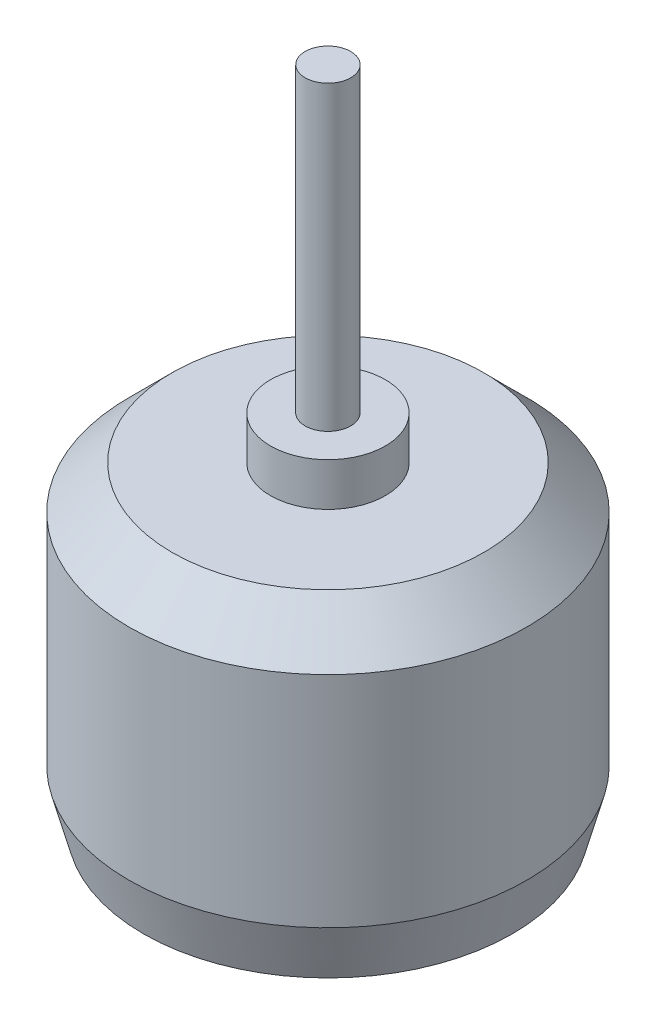
SolidWorks part; units mm, degrees
ref_plane "Front Plane" through (0, 0, 0) normal (0, 0, 1) x (1, 0, 0)
ref_plane "Top Plane" through (0, 0, 0) normal (0, 1, 0) x (1, 0, 0)
ref_plane "Right Plane" through (0, 0, 0) normal (1, 0, 0) x (0, 0, -1)
sketch "Sketch1" plane through (0, 0, 0) normal (0, 1, 0) x (1, 0, 0)
  circle A0 centre (0, 0) radius 13.85
  dimension "D1" = 27.7
extrude "Boss-Extrude1" add sketch "Sketch1" along normal blind 22
sketch "Sketch2" plane through (0, 22, 0) normal (0, 1, 0) x (1, 0, 0)
  circle A0 centre (0, 0) radius 4
  dimension "D1" = 8
extrude "Boss-Extrude2" add sketch "Sketch2" along normal blind 3
sketch "Sketch3" plane through (0, 25, 0) normal (0, 1, 0) x (1, 0, 0)
  circle A0 centre (0, 0) radius 1.5875
  dimension "D1" = 3.175
extrude "Boss-Extrude3" add sketch "Sketch3" along normal blind 11
chamfer "Chamfer1" distance 3 angle 45 1 edges at (0, 22, 13.85)
chamfer "Chamfer2" distance 1 angle 75 1 edges at (0, 0, 13.85) first distance on face at (0, 0, 13.85)
sketch "Sketch4" plane through (0, 0, 0) normal (0, -1, 0) x (1, 0, 0)
  circle A0 centre (0, 0) radius 3.25
  dimension "D1" = 6.5
extrude "Boss-Extrude4" add sketch "Sketch4" along normal blind 1
sketch "Sketch6" plane through (0, 0, 0) normal (0, -1, 0) x (1, 0, 0)
  line L0 (0, 0) -> (6.7175, 6.7175) construction
  line L1 (0, 0) -> (5.6569, -5.6569) construction
  line L2 (-5.6569, 5.6569) -> (0, 0) construction
  line L3 (0, 0) -> (-6.7175, -6.7175) construction
  line L4 (0, 0) -> (0, 3.25) construction
  circle A0 centre (0, 0) radius 3.25 construction
  dimension "D1" = 90
  dimension "D2" = 45
  dimension "D3" = 19
  dimension "D4" = 16
hole_wizard "M3x0.5 Tapped Hole1" positions "Sketch7" profile "Sketch8" tap size "M3x0.5" standard "ANSI Metric"
sketch "Sketch7" plane through (0, 0, 0) normal (0, -1, 0) x (-1, 0, 0)
  point P0 (5.6569, -5.6569)
  point P3 (-6.7175, -6.7175)
  point P6 (-5.6569, 5.6569)
  point P9 (6.7175, 6.7175)
sketch "Sketch8" plane through (-5.6569, 0, 5.6569) normal (1, 0, 0) x (0, 0, -1)
  line L0 (0, 0) -> (0, 8.2511)
  line L1 (0, 8.2511) -> (1.25, 7.5)
  line L2 (1.25, 7.5) -> (1.25, 0)
  line L5 (1.25, 0) -> (0, 0)
  line L10 (0, 8.2511) -> (-1.25, 7.5) construction
  line L11 (0, -6.35) -> (0, 107.95) construction
  dimension "Tap Drill Dia." = 2.5
  dimension "Tap Drill Depth" = 7.5
  dimension "Drill Angle" = 118
cosmetic thread "Hole Thread1" parameters "D1"=6, "D2"=3
cosmetic thread "Hole Thread2" parameters "D1"=6, "D2"=3
cosmetic thread "Hole Thread3" parameters "D1"=6, "D2"=3
cosmetic thread "Hole Thread4" parameters "D1"=6, "D2"=3
sketch "Sketch9" plane through (0, 36, 0) normal (0, 1, 0) x (1, 0, 0)
  circle A0 centre (0, 0) radius 1.5875
extrude "Boss-Extrude5" add sketch "Sketch9" along normal blind 10
